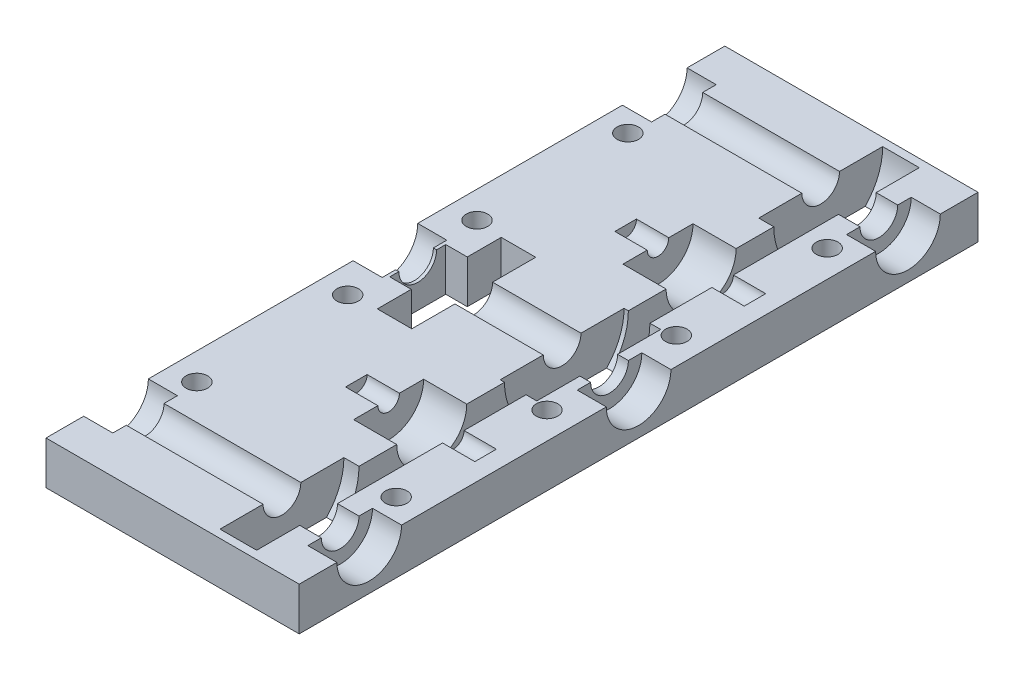
SolidWorks part; units mm, degrees
other "标注1"
sketch "草图3" plane through (-22.25, 4, -10) normal (-0.231, 0.6469, -0.7268) x (-0.9696, -0.2151, 0.1167)
ref_plane "前视基准面" through (0, 0, 0) normal (0, 0, 1) x (1, 0, 0)
ref_plane "上视基准面" through (0, 0, 0) normal (0, 1, 0) x (1, 0, 0)
ref_plane "右视基准面" through (0, 0, 0) normal (1, 0, 0) x (0, 0, -1)
other "Configuration Table"
sketch "草图4" plane through (0, 0, 0) normal (0, 1, 0) x (1, 0, 0)
  line L1 (-11.75, -31.5) -> (11.75, -31.5)
  line L2 (-11.75, -31.5) -> (-11.75, 31.5)
  line L3 (-11.75, 31.5) -> (11.75, 31.5)
  line L4 (11.75, -31.5) -> (11.75, 31.5)
  line L5 (-11.75, -31.5) -> (11.75, 31.5) construction
  line L6 (-11.75, 31.5) -> (11.75, -31.5) construction
  point P0 (0, 0)
  dimension "D1" = 63
  dimension "D2" = 23.5
extrude "凸台-拉伸1" add sketch "草图4" along normal blind 7
sketch "草图5" plane through (11.75, 0, 0) normal (1, 0, 0) x (0, 0, -1)
  line L0 (-31.5, 7) -> (31.5, 7) construction
  line L1 (-25, 7) -> (0, 7) construction
  line L2 (0, 7) -> (25, 7) construction
  circle A0 centre (-25, 7) radius 3
  circle A1 centre (0, 7) radius 3
  circle A2 centre (25, 7) radius 3
  circle A3 centre (-25, 7) radius 1.75
  circle A4 centre (0, 7) radius 1.75
  circle A5 centre (25, 7) radius 1.75
  dimension "D2" = 6
  dimension "D3" = 50
  dimension "D5" = 3.5
extrude "切除-拉伸1" cut sketch "草图5" against normal through all contours A3 | A5 | A4
extrude "切除-拉伸4" cut sketch "草图5<3>" against normal blind 2.7 contours A2 | A0
sketch "草图5<3>" plane through (11.75, 0, 0) normal (1, 0, 0) x (0, 0, -1) same geometry as "草图5"
extrude "切除-拉伸5" cut sketch "草图5<4>" along normal blind 2.7 from surface contours A0 | A2 starting at face at (-11.75, 5.075, 0)
sketch "草图5<4>" plane through (11.75, 0, 0) normal (1, 0, 0) x (0, 0, -1) same geometry as "草图5"
extrude "切除-拉伸6" cut sketch "草图5<5>" against normal blind 2.7 contours A1
sketch "草图5<5>" plane through (11.75, 0, 0) normal (1, 0, 0) x (0, 0, -1) same geometry as "草图5"
extrude "切除-拉伸7" cut sketch "草图5<6>" along normal blind 2.7 from surface contours A1 starting at face at (-11.75, 4.825, 0)
sketch "草图5<6>" plane through (11.75, 0, 0) normal (1, 0, 0) x (0, 0, -1) same geometry as "草图5"
sketch "草图6" plane through (0, 0, 0) normal (0, -1, 0) x (1, 0, 0)
  line L0 (-9.25, 0) -> (9.25, 0) construction
  line L1 (-11.75, -31.5) -> (-11.75, 31.5) construction
  line L3 (-9.25, 6) -> (-9.25, -6) construction
  line L4 (9.25, 20) -> (9.25, -20) construction
  circle A0 centre (-9.25, 6) radius 1.5
  circle A1 centre (9.25, 6) radius 1.5
  circle A2 centre (-9.25, -20) radius 1.5
  circle A3 centre (-9.25, -20) radius 1
  circle A4 centre (9.25, -20) radius 1.5
  circle A5 centre (9.25, -20) radius 1
  circle A6 centre (-9.25, 20) radius 1
  circle A7 centre (-9.25, 20) radius 1.5
  circle A8 centre (9.25, 20) radius 1.5
  circle A9 centre (9.25, 20) radius 1
  circle A10 centre (-9.25, -6) radius 1.5
  circle A11 centre (9.25, -6) radius 1.5
  circle A12 centre (9.25, -6) radius 1
  circle A13 centre (-9.25, -6) radius 1
  circle A14 centre (-9.25, 6) radius 1
  circle A15 centre (9.25, 6) radius 1
  dimension "D1" = 3
  dimension "D2" = 2
  dimension "D3" = 2.5
  dimension "D4" = 6
  dimension "D5" = 20
extrude "切除-拉伸2" cut sketch "草图6" against normal offset from surface (5 mm away) 2 up to face at (0, 7, 12.5)
extrude "切除-拉伸3" cut sketch "草图6<2>" against normal through all contours A3 | A13 | A6 | A15 | A12 | A5 | A14 | A9
sketch "草图6<2>" plane through (0, 0, 0) normal (0, -1, 0) x (1, 0, 0) same geometry as "草图6"
sketch "草图7" plane through (0, 7, 0) normal (0, 1, 0) x (1, 0, 0)
  line L0 (-16.0011, 0) -> (16.0011, 0)
ref_plane "基准面1" through (0, 0, 0) normal (0, 0, 1) x (1, 0, 0)
sketch "草图9" plane through (11.75, 0, 0) normal (1, 0, 0) x (0, 0, -1)
  line L0 (-12.9845, 12.5) -> (13.4782, 12.5)
  line L1 (-12.9845, 11.3) -> (12.3661, 11.3)
  line L3 (0, 7) -> (0, 0)
  line L4 (-31.5, 0) -> (31.5, 0) construction
  arc A0 (-3, 7) -> (3, 7) centre (0, 7) ccw construction
  dimension "D1" = 4.3
  dimension "D2" = 5.5
ref_plane "基准面2" through (0, 12.5, 0) normal (0, 1, 0) x (1, 0, 0)
ref_plane "基准面3" through (0, 11.3, 0) normal (0, 1, 0) x (1, 0, 0)
sketch "草图10" plane through (0, 7, 0) normal (0, 1, 0) x (1, 0, 0)
  line L0 (-8.75, 2.6) -> (-8.75, -2.6)
  line L1 (-8.75, -2.6) -> (-6.75, -2.6)
  line L2 (-6.75, -2.6) -> (-6.75, -5.75)
  line L3 (-6.75, -5.75) -> (-3.55, -5.75)
  line L4 (-3.55, -5.75) -> (-3.55, 5.75)
  line L5 (-3.55, 5.75) -> (-6.75, 5.75)
  line L6 (-6.75, 5.75) -> (-6.75, 2.6)
  line L7 (-6.75, 2.6) -> (-8.75, 2.6)
  line L8 (-9.05, 0) -> (-8.75, 0) construction
  line L9 (-9.05, 1.75) -> (-9.05, -1.75) construction
  dimension "D1" = 0.3
  dimension "D2" = 2
  dimension "D3" = 5.2
  dimension "D4" = 11.5
  dimension "D5" = 3.2
extrude "切除-拉伸8" cut sketch "草图10" against normal blind 6
sketch "草图12" plane through (9.05, 0, 0) normal (1, 0, 0) x (0, 0, -1)
  line L0 (-1.75, 7) -> (1.75, 7)
  line L1 (-1.75, 7) -> (-3, 7) construction
  line L2 (3, 7) -> (1.75, 7) construction
  circle A0 centre (0, 7) radius 5.75
  arc A1 (-1.75, 7) -> (1.75, 7) centre (0, 7) ccw construction
  dimension "D1" = 11.5
extrude "切除-拉伸9" cut sketch "草图12" against normal blind 3.4 from offset 1 contours A0 offset against normal yes
sketch "草图13" plane through (4.65, 0, 0) normal (1, 0, 0) x (0, 0, -1)
  line L0 (-22, 7) -> (-3, 7) construction
  line L1 (3, 7) -> (22, 7) construction
  line L2 (-12.5, 7) -> (12.5, 7) construction
  circle A0 centre (-12.5, 7) radius 8.25
  circle A1 centre (12.5, 7) radius 8.25
  dimension "D2" = 16.5
  dimension "D1" = 12.5
extrude "切除-拉伸10" cut sketch "草图13" along normal blind 2 from offset 0.4
sketch "草图14" plane through (5.05, 0, 0) normal (1, 0, 0) x (0, 0, -1)
  line L0 (-22, 7) -> (-3, 7) construction
  line L1 (3, 7) -> (22, 7) construction
  line L2 (-12.5, 7) -> (12.5, 7) construction
  circle A0 centre (-12.5, 7) radius 3.25
  arc A1 (-20.75, 7) -> (-16.8661, 0) centre (-12.5, 7) ccw construction
  circle A2 centre (12.5, 7) radius 3.25
  dimension "D1" = 6.5
extrude "切除-拉伸11" cut sketch "草图14" against normal blind 4
sketch "草图15" plane through (11.75, 0, 0) normal (1, 0, 0) x (0, 0, -1)
  line L0 (-22, 7) -> (-3, 7) construction
  line L1 (3, 7) -> (22, 7) construction
  line L2 (-12.5, 7) -> (12.5, 7) construction
  circle A0 centre (-12.5, 7) radius 1
  arc A1 (-15.75, 7) -> (-9.25, 7) centre (-12.5, 7) ccw construction
  circle A2 centre (12.5, 7) radius 1
  dimension "D1" = 2
extrude "切除-拉伸12" cut sketch "草图15" along normal blind 3 from surface starting at face at (7.05, 3.4168, 11.4332)
extrude "切除-拉伸15" cut sketch "草图15<2>" against normal blind 3 from surface starting at face at (1.05, 5.375, 12.5)
sketch "草图15<2>" plane through (11.75, 0, 0) normal (1, 0, 0) x (0, 0, -1) same geometry as "草图15"
sketch "草图16" plane through (7.05, 0, 0) normal (-1, 0, 0) x (0, 0, 1)
  line L0 (-25, 7) -> (25, 7) construction
  circle A0 centre (25, 7) radius 5.75
  arc A1 (22, 7) -> (28, 7) centre (25, 7) ccw construction
  circle A2 centre (-25, 7) radius 5.75
  dimension "D1" = 11.5
extrude "切除-拉伸13" cut sketch "草图16" along normal blind 3.4
sketch "草图17" plane through (0, 0, 0) normal (0, -1, 0) x (1, 0, 0)
  line L0 (-11.75, 31.5) -> (11.75, 31.5) construction
  line L1 (-11.75, 31.5) -> (11.75, 31.5)
  line L2 (-11.75, 31.5) -> (-11.75, -31.5)
  line L3 (-11.75, -31.5) -> (11.75, -31.5)
  line L4 (11.75, 31.5) -> (11.75, -31.5)
  line L5 (-11.75, -31.5) -> (-11.75, 31.5) construction
  line L6 (11.75, -31.5) -> (-11.75, -31.5) construction
  line L7 (11.75, 31.5) -> (11.75, -31.5) construction
extrude "切除-拉伸14" cut sketch "草图17" against normal offset from surface (3 mm away) 4 up to face at (-9.25, 7, 5)
